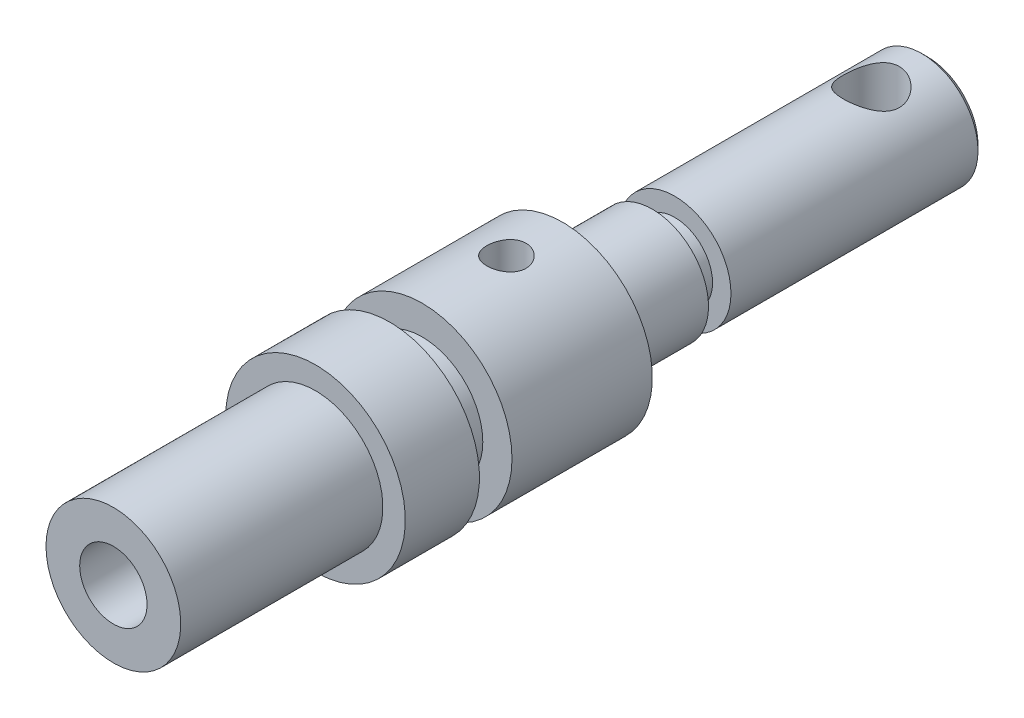
SolidWorks part; units mm, degrees
ref_plane "Face" through (0, 0, 0) normal (0, 0, 1) x (1, 0, 0)
ref_plane "Dessus" through (0, 0, 0) normal (0, 1, 0) x (1, 0, 0)
ref_plane "Droite" through (0, 0, 0) normal (1, 0, 0) x (0, 0, -1)
ref_axis "Axe1" through (0, 0, 50) along (0, 0, -1)
sketch "Esquisse2" plane through (0, 0, 0) normal (1, 0, 0) x (0, 0, -1)
  line L0 (0, -3) -> (0, -6)
  line L4 (0, -6) -> (18, -6)
  line L5 (18, -6) -> (18, -8)
  line L6 (40, -5) -> (72.5, -5)
  line L8 (72.5, -5) -> (72.5, 0)
  line L9 (40, -5) -> (40, -8)
  line L13 (0, -3) -> (41, -3)
  line L14 (41, -3) -> (42.7321, 0)
  line L15 (42.7321, 0) -> (72.5, 0)
  line L24 (40, -8) -> (18, -8)
  line L25 (0, 0) -> (-26.6206, 0) construction
  dimension "D1" = 60
  dimension "D2" = 41
  dimension "D3" = 22
  dimension "D4" = 40
  dimension "D5" = 6
  dimension "D6" = 12
  dimension "D7" = 32.5
revolve "Base-Révolution" add sketch "Esquisse2" angle 360 about L25
ref_plane "Plan1" through (0, 0, -35) normal (0, 0, -1) x (-1, 0, 0)
ref_axis "Axe2" through (0, -50, -35) along (0, 1, 0)
sketch "Esquisse3" plane through (0, 0, -35) normal (0, 0, -1) x (-1, 0, 0)
  line L0 (0, 0) -> (0, -10.6306) construction
  line L1 (0, -8.8218) -> (-1.75, -8.8218)
  line L2 (0, -8.8218) -> (0, 9.393)
  line L3 (0, 9.393) -> (-1.75, 9.393)
  line L4 (-1.75, -8.8218) -> (-1.75, 9.393)
  dimension "D1" = 1.75
revolve "Enlèvement de matière-Révolution1" cut sketch "Esquisse3" angle 360 about L0
ref_plane "Plan2" through (0, 0, -67.5) normal (0, 0, -1) x (-1, 0, 0)
ref_axis "Axe3" through (0, -50, -67.5) along (0, 1, 0)
chamfer "Chanfrein1" distance 0.5 angle 45 1 edges at (-5, 0, -72.5)
sketch "Esquisse6" plane through (0, 0, 0) normal (0, 1, 0) x (1, 0, 0)
  circle A0 centre (0, 67.5) radius 2.5 construction
  circle A1 centre (0, 67.5) radius 2.5
  circle A2 centre (0, 67.5) radius 2.5 construction
extrude "Enlèv. mat.-Extru.1" cut sketch "Esquisse6" against normal mid plane 15
ref_plane "Pland'appui joint1" through (0, 0, -50) normal (0, 0, 1) x (1, 0, 0)
ref_plane "Plan d'appui joint2" through (0, 0, -27.5) normal (0, 0, -1) x (-1, 0, 0)
sketch "Esquisse5" plane through (0, 0, 0) normal (1, 0, 0) x (0, 0, -1)
  line L0 (-18.4286, 0) -> (12.5012, 0) construction
  line L1 (27.5, -50) -> (27.5, 50) construction
  line L2 (50, 50) -> (50, -50) construction
  line L3 (24.6, 30) -> (24.6, 5.4)
  line L4 (24.6, 5.4) -> (27.5, 5.4)
  line L5 (27.5, 5.4) -> (27.5, 20)
  line L6 (27.5, 20) -> (48, 20)
  line L7 (48, 20) -> (48, 3.36)
  line L8 (48, 3.36) -> (50, 3.36)
  line L9 (50, 3.36) -> (50, 30)
  line L10 (50, 30) -> (24.6, 30)
  dimension "D1" = 20
  dimension "D2" = 2.9
  dimension "D3" = 5.4
  dimension "D5" = 2
  dimension "D6" = 3.36
revolve "Enlèvement de matière-Révolution3" cut sketch "Esquisse5" angle 360 about L0
